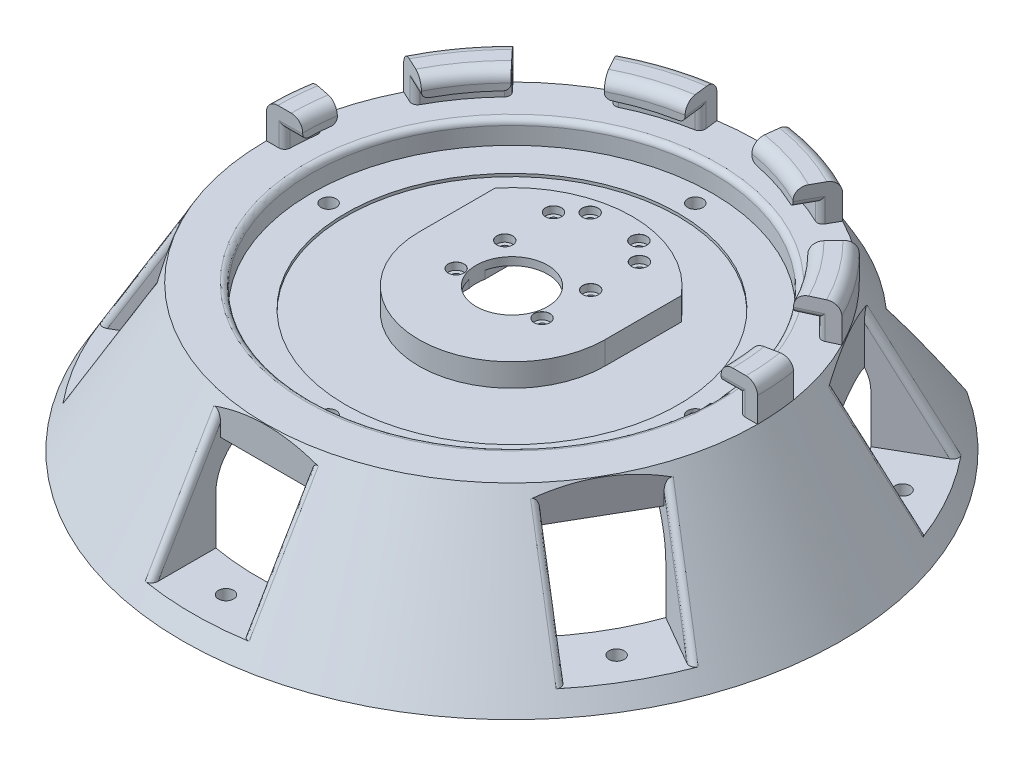
SolidWorks part; units mm, degrees
note: The reader was unsure of these and kept them because the rebuilt part matched: shared geometry of "Sketch3<3>".
material "PLA"
ref_plane "Front Plane" through (0, 0, 0) normal (0, 0, 1) x (1, 0, 0)
ref_plane "Top Plane" through (0, 0, 0) normal (0, 1, 0) x (1, 0, 0)
ref_plane "Right Plane" through (0, 0, 0) normal (1, 0, 0) x (0, 0, -1)
sketch "Sketch1" plane through (0, 0, 0) normal (0, 0, 1) x (1, 0, 0)
  line L0 (0, 0) -> (-85.725, 0)
  line L1 (-85.725, 0) -> (-115.0544, -50.8)
  line L2 (-115.0544, -50.8) -> (0, -50.8)
  line L6 (0, 0) -> (0, -50.8) construction
  line L7 (0, 0) -> (0, -50.8)
  dimension "D1" = 85.725
  dimension "D3" = 50.8
  dimension "D4" = 60
revolve "Revolve1" add sketch "Sketch1" angle 360 about L6
sketch "Sketch2" plane through (0, 0, 0) normal (0, 1, 0) x (1, 0, 0)
  circle A0 centre (0, 0) radius 12.5
  dimension "D1" = 25
extrude "Cut-Extrude1" cut sketch "Sketch2" against normal through all
sketch "Sketch3" plane through (0, 0, 0) normal (0, 1, 0) x (1, 0, 0)
  line L0 (-32.5, 0) -> (-32.5, 26.6036)
  line L1 (-32.5, 26.6036) -> (32.5, 26.6036)
  line L2 (32.5, 26.6036) -> (32.5, 0)
  circle A0 centre (0, 0) radius 32.5
  circle A1 centre (0, 0) radius 70
  circle A2 centre (0, 0) radius 42
  circle M1 centre (0, 0) radius 12.5
  dimension "D1" = 65
  dimension "D2" = 140
  dimension "D3" = 84
extrude "Cut-Extrude2" cut sketch "Sketch3" against normal blind 8 contours A1 A0 L0 L1 L2 | A1 A2
sketch "Sketch7" plane through (0, -50.8, 0) normal (0, -1, 0) x (1, 0, 0)
  line L0 (0, 88.9) -> (0, -161.1) construction
  line L1 (-85.4, 0) -> (85.4, 0) construction
  line L2 (-60, -65.5989) -> (-60, -161.1)
  line L3 (-60, -161.1) -> (60, -161.1)
  line L4 (60, -161.1) -> (60, -65.5989)
  line L5 (-60, -65.5989) -> (60, -65.5989) construction
  arc A2 (60, -65.5989) -> (-60, -65.5989) centre (0, 0) ccw
  dimension "D1" = 177.8
  dimension "D2" = 25.4
  dimension "D3" = 25.4
  dimension "D4" = 120
  dimension "D5" = 250
extrude "Cut-Extrude5" cut sketch "Sketch7" against normal blind 39 contours L3 L4 A2 L2
sketch "Sketch8" plane through (0, 0, 0) normal (0, 1, 0) x (1, 0, 0)
  line L0 (0, 0) -> (0, -115.0544) construction
  line L2 (-15.875, -123.925) -> (15.875, -123.925)
  line L3 (-15.875, -123.925) -> (-15.875, -85.825)
  line L4 (-15.875, -85.825) -> (15.875, -85.825)
  line L5 (15.875, -123.925) -> (15.875, -85.825)
  line L6 (-15.875, -123.925) -> (15.875, -85.825) construction
  line L7 (-15.875, -85.825) -> (15.875, -123.925) construction
  arc A0 (-60, 98.1708) -> (60, 98.1708) centre (0, 0) ccw construction
  point P6 (0, -104.875)
  dimension "D1" = 85.825
  dimension "D2" = 38.1
  dimension "D3" = 31.75
extrude "Cut-Extrude6" cut sketch "Sketch8" against normal blind 44.45
pattern_circular "CirPattern2" count 6 over 360 about axis through (0, 0, 0) along (0, 1, 0) of "Cut-Extrude6"
sketch "Sketch9" plane through (0, 0, 0) normal (0, 1, 0) x (1, 0, 0)
  line L0 (0, 0) -> (0, -115.0544) construction
  arc A0 (-60, 98.1708) -> (60, 98.1708) centre (0, 0) ccw construction
  circle A1 centre (0, -99.8144) radius 2.65
  dimension "D1" = 5.3
  dimension "D2" = 15.24
extrude "Cut-Extrude7" cut sketch "Sketch9" against normal through all
pattern_circular "CirPattern3" count 6 over 360 about axis through (0, 0, 0) along (0, 1, 0) of "Cut-Extrude7"
sketch "Sketch12" plane through (0, 0, 0) normal (0, 0, 1) x (1, 0, 0)
  line L0 (85.725, 0) -> (85.725, 12.7)
  line L1 (85.725, 12.7) -> (73.025, 12.7)
  line L2 (73.025, 12.7) -> (73.025, 6.35)
  line L3 (73.025, 6.35) -> (79.375, 6.35)
  line L4 (79.375, 6.35) -> (79.375, 0)
  line L5 (85.725, 0) -> (-85.725, 0) construction
  line L6 (0, 0) -> (0, 12.7) construction
  line L7 (12.5, 0) -> (-12.5, 0) construction
  line L8 (79.375, 0) -> (85.725, 0)
  point P13 (0, 6.35)
  dimension "D1" = 6.35
  dimension "D2" = 73.025
  dimension "D3" = 79.375
  dimension "D4" = 12.7
  dimension "D5" = 12.7
revolve "Revolve2" add sketch "Sketch12" angle 180 about L6
sketch "Sketch15" plane through (0, -11.8, 0) normal (0, -1, 0) x (1, 0, 0)
  line L0 (0, -1000) -> (0, 49000) construction
  point P1 (-15, 4.5)
  point P4 (-15, -12.5)
  point P5 (-15, -29.5)
  point P6 (-8.5, -35.8)
  point P7 (8.5, -35.8)
  point P8 (15, -29.5)
  point P9 (15, -12.5)
  point P10 (15, 4.5)
  dimension "D1" = 17
  dimension "D2" = 17
  dimension "D3" = 4.5
  dimension "D4" = 15
  dimension "D5" = 8.5
  dimension "D6" = 35.8
sketch "Sketch18" plane through (0, 12.7, 0) normal (0, 1, 0) x (1, 0, 0)
  line L0 (46.6433, 89.7185) -> (70.9138, 72.0849)
  line L1 (0, 201000) -> (0, -249000) construction
  line L2 (-15, 100) -> (-9, 50)
  line L3 (-9, 50) -> (9, 50)
  line L4 (9, 50) -> (15, 100)
  line L5 (-15, 100) -> (15, 100)
  line L6 (36.6704, 35.1608) -> (70.9138, 72.0849)
  line L7 (22.1081, 45.7409) -> (36.6704, 35.1608)
  line L8 (46.6433, 89.7185) -> (22.1081, 45.7409)
  line L9 (90.4704, 45.1675) -> (99.7409, 16.6359)
  line L10 (50.334, 6.8913) -> (99.7409, 16.6359)
  line L11 (44.7717, 24.0104) -> (50.334, 6.8913)
  line L12 (90.4704, 45.1675) -> (44.7717, 24.0104)
  line L13 (99.7409, -16.6359) -> (90.4704, -45.1675)
  line L14 (44.7717, -24.0104) -> (90.4704, -45.1675)
  line L15 (50.334, -6.8913) -> (44.7717, -24.0104)
  line L16 (99.7409, -16.6359) -> (50.334, -6.8913)
  line L17 (70.9138, -72.0849) -> (46.6433, -89.7185)
  line L18 (22.1081, -45.7409) -> (46.6433, -89.7185)
  line L19 (36.6704, -35.1608) -> (22.1081, -45.7409)
  line L20 (70.9138, -72.0849) -> (36.6704, -35.1608)
  line L21 (15, -100) -> (-15, -100)
  line L22 (-9, -50) -> (-15, -100)
  line L23 (9, -50) -> (-9, -50)
  line L24 (15, -100) -> (9, -50)
  line L25 (-46.6433, -89.7185) -> (-70.9138, -72.0849)
  line L26 (-36.6704, -35.1608) -> (-70.9138, -72.0849)
  line L27 (-22.1081, -45.7409) -> (-36.6704, -35.1608)
  line L28 (-46.6433, -89.7185) -> (-22.1081, -45.7409)
  line L29 (-90.4704, -45.1675) -> (-99.7409, -16.6359)
  line L30 (-50.334, -6.8913) -> (-99.7409, -16.6359)
  line L31 (-44.7717, -24.0104) -> (-50.334, -6.8913)
  line L32 (-90.4704, -45.1675) -> (-44.7717, -24.0104)
  line L33 (-99.7409, 16.6359) -> (-90.4704, 45.1675)
  line L34 (-44.7717, 24.0104) -> (-90.4704, 45.1675)
  line L35 (-50.334, 6.8913) -> (-44.7717, 24.0104)
  line L36 (-99.7409, 16.6359) -> (-50.334, 6.8913)
  line L37 (-70.9138, 72.0849) -> (-46.6433, 89.7185)
  line L38 (-22.1081, 45.7409) -> (-46.6433, 89.7185)
  line L39 (-36.6704, 35.1608) -> (-22.1081, 45.7409)
  line L40 (-70.9138, 72.0849) -> (-36.6704, 35.1608)
  point P4 (0, 50)
  point P7 (0, 100)
  point P48 (0, 0)
  dimension "D1" = 18
  dimension "D2" = 50
  dimension "D3" = 30
  dimension "D4" = 50
  dimension "D5" = 10
extrude "Cut-Extrude9" cut sketch "Sketch18" against normal blind 12.7
sketch "Sketch20" plane through (0, -11.8, 0) normal (0, -1, 0) x (1, 0, 0)
  line L0 (-22.5, -33) -> (-12.5, -40)
  line L1 (22.5, 23) -> (-22.5, 23)
  line L2 (22.5, 23) -> (22.5, -40)
  line L3 (22.5, -40) -> (-22.5, -40)
  line L4 (-22.5, 23) -> (-22.5, -40)
  line L7 (-12.5, -40) -> (12.5, -40)
  line L8 (12.5, -40) -> (22.5, -33)
  point P0 (0, -10)
  dimension "D1" = 23
  dimension "D2" = 45
  dimension "D3" = 10
  dimension "D4" = 10
  dimension "D5" = 7
  dimension "D6" = 7
  dimension "D7" = 10
  dimension "D8" = 40
  dimension "D9" = 22.5
extrude "Cut-Extrude11" cut sketch "Sketch3<3>" against normal blind 1 contours A0 L1 M1 | A0 L1 L0 | L1 A0 | L1 A2 A0 | A0 L2 L1
sketch "Sketch3<3>" plane through (0, 0, 0) normal (0, 1, 0) x (1, 0, 0) same geometry as "Sketch3"
sketch "Sketch22" plane through (0, -1, 0) normal (0, 1, 0) x (1, 0, 0)
  circle A0 centre (-15, 12.5) radius 1.4
  circle A1 centre (-15, 29.5) radius 1.4
  circle A2 centre (-8.5, 35.8) radius 1.4
  circle A3 centre (8.5, 35.8) radius 1.4
  circle A4 centre (15, 29.5) radius 1.4
  circle A5 centre (15, 12.5) radius 1.4
  circle A6 centre (15, -4.5) radius 1.4
  circle A7 centre (-15, -4.5) radius 1.4
  dimension "D1" = 17
  dimension "D2" = 17
  dimension "D3" = 2.8
  dimension "D4" = 2.8
  dimension "D5" = 2.8
  dimension "D6" = 2.8
  dimension "D7" = 2.8
  dimension "D8" = 2.8
  dimension "D9" = 2.8
  dimension "D10" = 2.8
  dimension "D11" = 17
  dimension "D12" = 30
  dimension "D13" = 30
  dimension "D14" = 30
  dimension "D15" = 17
  dimension "D16" = 17
  dimension "D17" = 6.3
  dimension "D18" = 6.3
  dimension "D19" = 35.8
  dimension "D20" = 8.5
  dimension "D21" = 35.8
  dimension "D22" = 15
  dimension "D23" = 19.5256
  dimension "D24" = 15.6605
hole_wizard "CBORE for M2.5 SHCS1" positions "Sketch23" profile "Sketch24" counterbore size "M2.5" standard "ANSI Metric" end condition through all
sketch "Sketch23" plane through (0, -1, 0) normal (0, 1, 0) x (1, 0, 0)
  point P0 (-15, -4.5)
  point P3 (-15, 12.5)
  point P6 (-15, 29.5)
  point P9 (-8.5, 35.8)
  point P12 (8.5, 35.8)
  point P15 (15, 29.5)
  point P18 (15, 12.5)
  point P21 (15, -4.5)
sketch "Sketch24" plane through (-15, -1, 4.5) normal (1, 0, 0) x (0, 0, 1)
  line L0 (0, 0) -> (0, 49.8)
  line L1 (0, 49.8) -> (1.45, 49.8)
  line L3 (1.45, 49.8) -> (1.45, 2.5)
  line L4 (2.75, 2.5) -> (1.45, 2.5)
  line L5 (2.75, 2.5) -> (2.75, 0.025)
  line L6 (2.75, 0.025) -> (2.775, 0)
  line L7 (2.775, 0) -> (0, 0)
  line L8 (-2.75, 0.025) -> (-2.775, 0) construction
  line L11 (0, -6.35) -> (0, 107.95) construction
  dimension "Thru Hole Dia." = 2.9
  dimension "Thru Hole Depth" = 49.8
  dimension "C'Bore Dia." = 5.5
  dimension "C'Bore Depth" = 2.5
  dimension "Near C'Sink Dia." = 5.55
  dimension "Near C'Sink Angle" = 90
fillet "Fillet1" radius 4 12 edges at (85.4509, 12.7, -6.8497) (69.353, 12.7, -50.3879) (26.4905, 12.7, -81.5293) (-26.4905, 12.7, -81.5293) (-69.353, 12.7, -50.3879) (-85.4509, 12.7, -6.8497) (-72.8088, 12.7, -5.6148) (-59.0785, 12.7, -42.923) (-22.566, 12.7, -69.4509) (22.566, 12.7, -69.4509) (59.0785, 12.7, -42.923) (72.8088, 12.7, -5.6148)
fillet "Fillet2" radius 2 12 edges at (75.2789, 6.35, -11.8112) (76.2, 6.35, 0) (53.9595, 6.35, -53.8033) (67.8444, 6.35, -34.6924) (12.0293, 6.35, -75.2444) (34.4956, 6.35, -67.9447) (-12.0293, 6.35, -75.2444) (-34.4956, 6.35, -67.9447) (-53.9595, 6.35, -53.8033) (-67.8444, 6.35, -34.6924) (-75.2789, 6.35, -11.8112) (-76.2, 6.35, 0)
fillet "Fillet3" radius 2 12 edges at (-78.3963, 4.175, -12.4261) (-56.1201, 4.175, -56.1331) (-70.7278, 4.175, -36.0273) (-12.4079, 4.175, -78.3992) (56.1201, 4.175, -56.1331) (78.3963, 4.175, -12.4261) (-79.375, 4.175, 0) (-36.0437, 4.175, -70.7195) (12.4079, 4.175, -78.3992) (36.0437, 4.175, -70.7195) (70.7278, 4.175, -36.0273) (79.375, 4.175, 0)
fillet "Fillet4" radius 2 10 edges
fillet "Fillet5" radius 2 1 edges at (0, 0, 70)
fillet "Fillet6" radius 16 4 edges at (88.9, -11.8, 0) (-88.9, -11.8, 0) (-44.45, -11.8, 76.9897) (44.45, -11.8, 76.9897)
fillet "Fillet7" radius 16 1 edges at (64.036, -11.8, -61.6652)
fillet "Fillet8" radius 16 1 edges at (-64.036, -11.8, -61.6652)
fillet "Fillet9" radius 1 2 edges
sketch "Sketch28" plane through (0, -11.8, 0) normal (0, -1, 0) x (1, 0, 0)
  line L0 (9.2, 12) -> (-9.2, 12)
  line L1 (-12.2, 9) -> (-12.2, -30)
  line L2 (-9.2, -33) -> (9.2, -33)
  line L3 (12.2, -30) -> (12.2, 9)
  arc A0 (-9.2, 12) -> (-12.2, 9) centre (-9.2, 9) ccw
  arc A1 (-12.2, -30) -> (-9.2, -33) centre (-9.2, -30) ccw
  arc A2 (9.2, -33) -> (12.2, -30) centre (9.2, -30) ccw
  arc A3 (12.2, 9) -> (9.2, 12) centre (9.2, 9) ccw
extrude "Cut-Extrude12" cut sketch "Sketch28" against normal offset from surface (8.05 mm away) 2.75
extrude "Cut-Extrude15" cut sketch "Sketch20" against normal offset from surface (5.3 mm away) 2.75
sketch "Sketch29" plane through (0, -8, 0) normal (0, 1, 0) x (1, 0, 0)
  point P0 (0, 64)
  point P5 (64, 0)
  point P6 (0, -64)
  point P7 (-64, 0)
  point P8 (0, 0)
  dimension "D1" = 64
  dimension "D2" = 4
hole_wizard "M5 Clearance Hole1" positions "Sketch32" profile "Sketch33" hole size "M5" standard "ANSI Metric" end condition up to next
sketch "Sketch32" plane through (0, -8, 0) normal (0, 1, 0) x (1, 0, 0)
  point P0 (0, 64)
  point P3 (64, 0)
  point P6 (0, -64)
  point P9 (-64, 0)
sketch "Sketch33" plane through (0, -8, -64) normal (1, 0, 0) x (0, 0, 1)
  line L0 (0, 0) -> (0, 3.8)
  line L1 (0, 3.8) -> (2.65, 3.8)
  line L2 (2.65, 3.8) -> (2.65, 0)
  line L5 (2.65, 0) -> (0, 0)
  line L11 (0, -6.35) -> (0, 107.95) construction
  dimension "Thru Hole Dia." = 5.3
  dimension "Thru Hole Depth" = 3.8
sketch "Sketch34" plane through (0, -8, 0) normal (0, 1, 0) x (1, 0, 0)
  circle A0 centre (0, 0) radius 70
  circle A1 centre (0, 0) radius 58
  line M5 (-32.5, 0) -> (-32.5, 26.6036)
  arc M6 (-32.5, 26.6036) -> (32.5, 26.6036) centre (0, 0) cw
  line M7 (32.5, 26.6036) -> (32.5, 0)
  arc M8 (32.5, 0) -> (-32.5, 0) centre (0, 0) cw
  dimension "D1" = 140
  dimension "D2" = 116
extrude "Cut-Extrude16" cut sketch "Sketch34" against normal blind 1 contours A1 M8 M5 M6 M7
